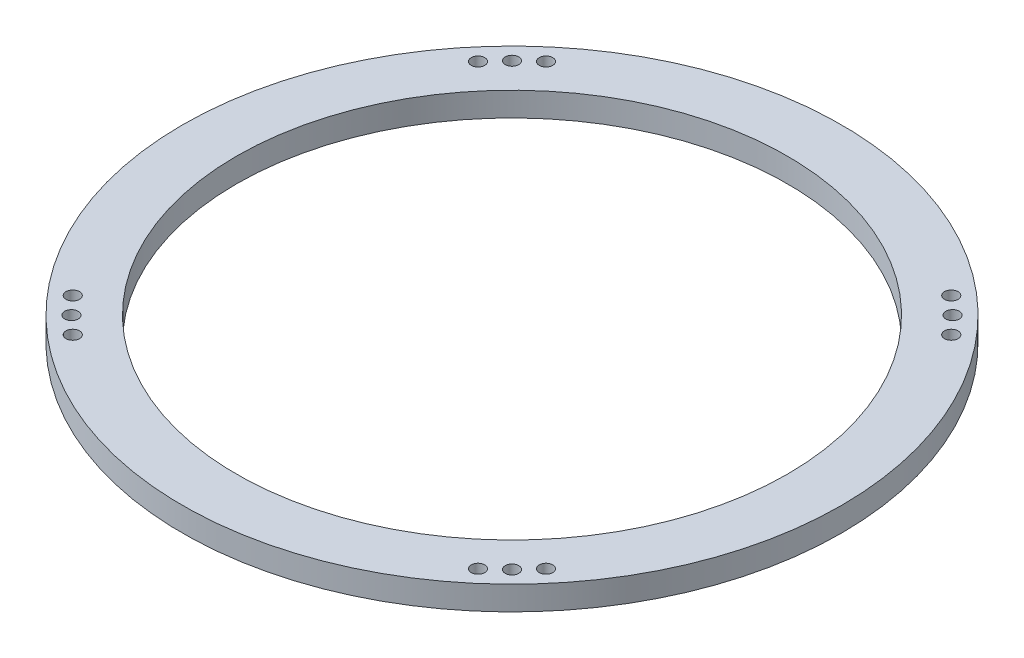
SolidWorks part; units mm, degrees
material "Oak"
ref_plane "Front Plane" through (0, 0, 0) normal (0, 0, 1) x (1, 0, 0)
ref_plane "Top Plane" through (0, 0, 0) normal (0, 1, 0) x (1, 0, 0)
ref_plane "Right Plane" through (0, 0, 0) normal (1, 0, 0) x (0, 0, -1)
sketch "Sketch1" plane through (0, 0, 0) normal (0, 0, 1) x (1, 0, 0)
  line L0 (0, -200000) -> (0, 218797.9879) construction
  line L5 (0, -200000) -> (0, 218797.9879) construction
  line L6 (174.1012, 206.3724) -> (174.1012, 193.6724)
  line L7 (145.5262, 206.3724) -> (174.1012, 206.3724)
  line L8 (174.1012, 193.6724) -> (145.5262, 193.6724)
  line L9 (145.5262, 193.6724) -> (145.5262, 206.3724)
revolve "Revolve1" add sketch "Sketch1" angle 360 about L5
hole_wizard "9/32 (0.28125) Diameter Hole1" positions "Sketch5" profile "Sketch6" hole size "9/32" standard "ANSI Inch" end condition through all
sketch "Sketch5" plane through (0, 206.3724, 0) normal (0, 1, 0) x (1, 0, 0)
  point P0 (-116.373, 116.373)
  point P3 (-107.0457, 125.0062)
  point P6 (-125.0062, 107.0457)
sketch "Sketch6" plane through (-116.373, 206.3724, -116.373) normal (1, 0, 0) x (0, 0, 1)
  line L0 (0, 0) -> (0, 12.7)
  line L1 (0, 12.7) -> (3.5719, 12.7)
  line L2 (3.5719, 12.7) -> (3.5719, 0)
  line L5 (3.5719, 0) -> (0, 0)
  line L11 (0, -6.35) -> (0, 107.95) construction
  dimension "Thru Hole Dia." = 7.1437
  dimension "Thru Hole Depth" = 12.7
pattern_circular "CirPattern1" count 4 over 360 about axis through (0, -200000, 0) along (0, -1, 0) of "9/32 (0.28125) Diameter Hole1"
